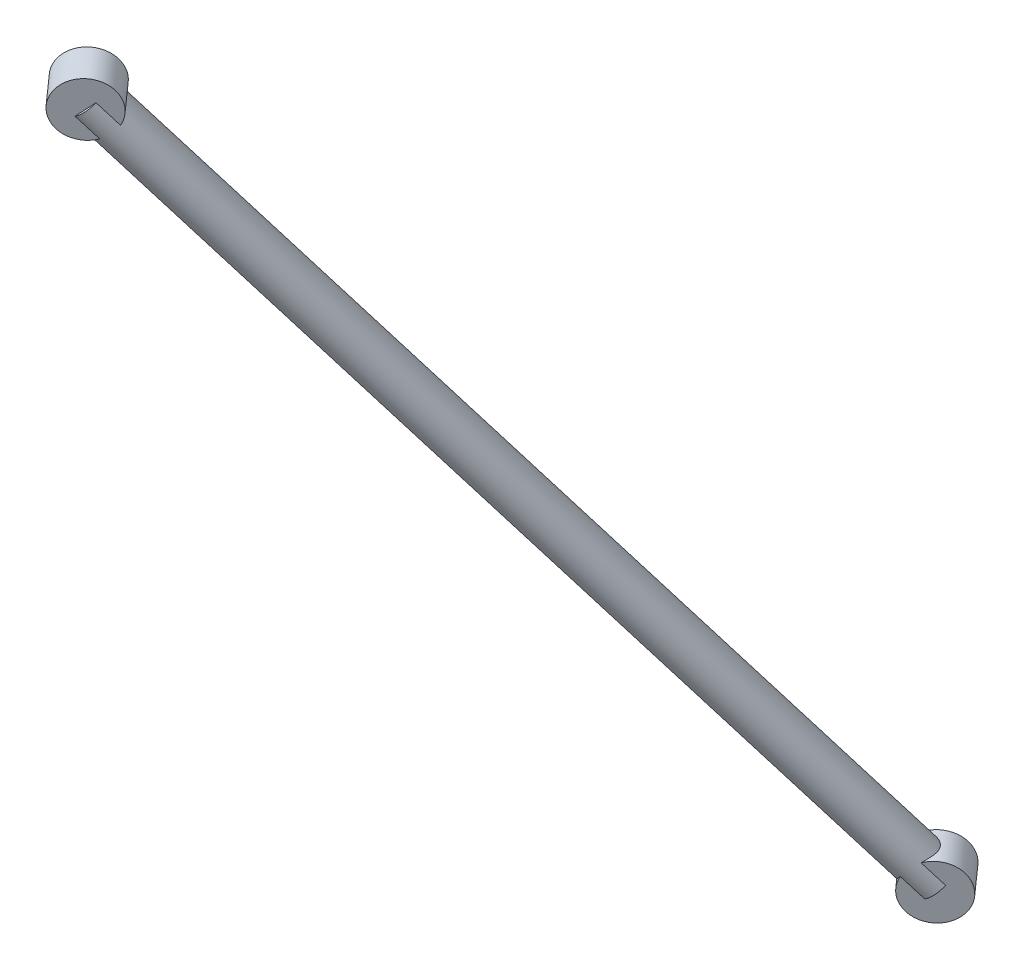
SolidWorks part; units mm, degrees
ref_plane "Plano frontal" through (0, 0, 0) normal (0, 0, 1) x (1, 0, 0)
ref_plane "Plano superior" through (0, 0, 0) normal (0, 1, 0) x (1, 0, 0)
ref_plane "Plano direito" through (0, 0, 0) normal (1, 0, 0) x (0, 0, -1)
sketch3d "SUSP_RL_pushrod_eixo"
  line L0 (-503.54, 1408.46, -83.29) -> (-338.5589, 1141.1054, -251.4325)
sweep "SUSP_RL_pushrod" add path "SUSP_RL_pushrod_eixo" circular profile diameter 16 parameters "D3"=16
sketch3d "SUSP_RL_pushrod_rod_end_mount_eixo"
  line L0 (-498.926, 1408.0085, -78.0453) -> (-508.154, 1408.9115, -88.5347)
sweep "SUSP_RL_pushrod_rod_end_mount" add path "SUSP_RL_pushrod_rod_end_mount_eixo" circular profile diameter 22 parameters "D3"=22
sketch3d "SUSP_RL_pushrod_rod_end_rocker_eixo"
  line L0 (-333.9449, 1140.6539, -246.1878) -> (-343.1729, 1141.5569, -256.6772)
sweep "SUSP_RL_pushrod_rod_end_rocker" add path "SUSP_RL_pushrod_rod_end_rocker_eixo" circular profile diameter 22 parameters "D3"=22
sketch3d "REF_SKETCH"
  line L0 (-507.54, 1406.06, -85.09) -> (-499.54, 1410.86, -81.49)
  line L1 (-501.14, 1405.46, -86.49) -> (-505.94, 1411.46, -80.09)
  line L2 (-342.5589, 1138.7054, -253.2325) -> (-334.5589, 1143.5054, -249.6325)
  line L3 (-336.1589, 1138.1054, -254.6325) -> (-340.9589, 1144.1054, -248.2325)
ref_point "P_MOUNT"
ref_point "P_ROCKER"
